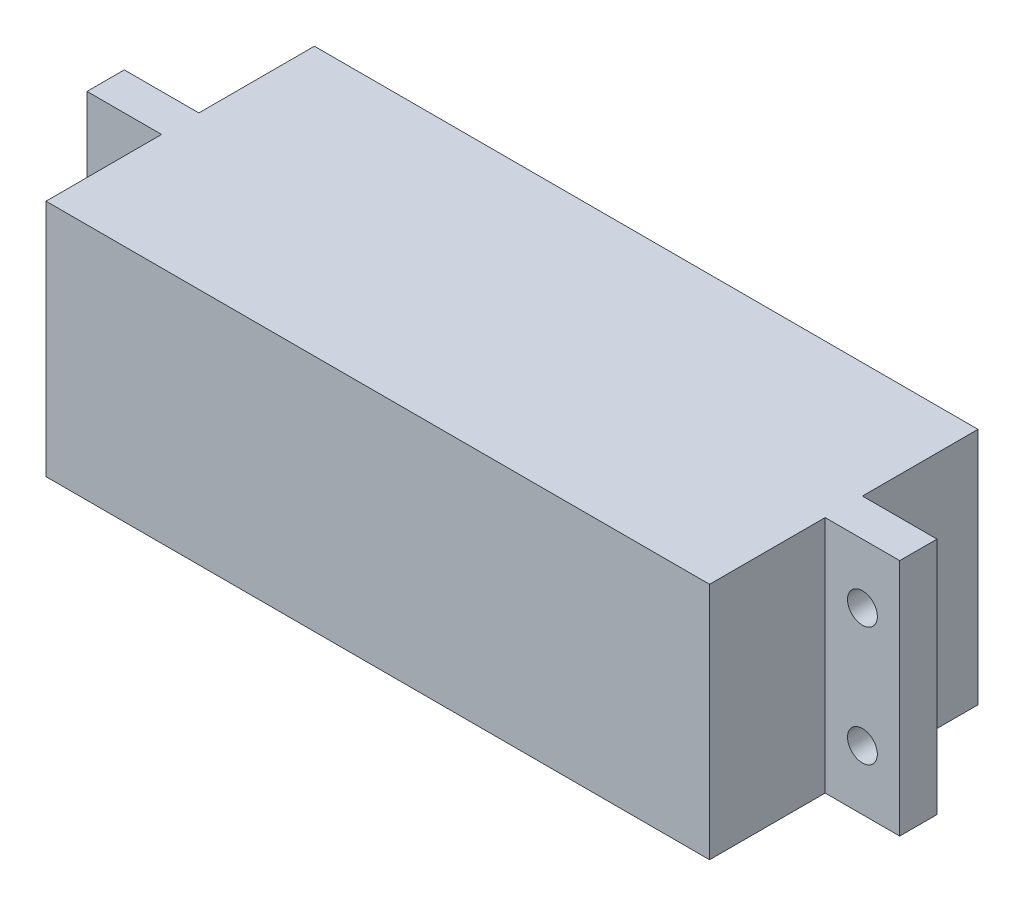
SolidWorks part; units mm, degrees
ref_plane "Front Plane" through (0, 0, 0) normal (0, 0, 1) x (1, 0, 0)
ref_plane "Top Plane" through (0, 0, 0) normal (0, 1, 0) x (1, 0, 0)
ref_plane "Right Plane" through (0, 0, 0) normal (1, 0, 0) x (0, 0, -1)
sketch "Sketch2" plane through (0, 0, 0) normal (0, 1, 0) x (1, 0, 0)
  line L1 (-42.5, -16) -> (42.5, -16)
  line L2 (-42.5, -16) -> (-42.5, 16)
  line L3 (-42.5, 16) -> (42.5, 16)
  line L4 (42.5, -16) -> (42.5, 16)
  line L5 (-42.5, -16) -> (42.5, 16) construction
  line L6 (-42.5, 16) -> (42.5, -16) construction
  point P0 (0, 0)
  dimension "D1" = 85
  dimension "D2" = 32
extrude "Boss-Extrude1" add sketch "Sketch2" along normal blind 2
extrude "Extrude-Thin1" add sketch "Sketch2<2>" along normal up to surface (2 mm away) and the other way blind 30 thin up to face at (0, 2, 0) thin type one direction wall 2
sketch "Sketch2<2>" plane through (0, 0, 0) normal (0, 1, 0) x (1, 0, 0) same geometry as "Sketch2"
sketch "Sketch3" plane through (44.5, 0, 0) normal (1, 0, 0) x (0, 0, -1)
  line L0 (18, 2) -> (-18, 2) construction
  line L1 (-2.5, 2) -> (2.5, 2)
  line L2 (-2.5, 2) -> (-2.5, -30)
  line L3 (-2.5, -30) -> (2.5, -30)
  line L4 (2.5, 2) -> (2.5, -30)
  line L5 (-18, -30) -> (18, -30) construction
  line L6 (-2.5, 2) -> (2.5, -30) construction
  line L7 (0, -30) -> (0, 2) construction
  point P12 (0, -14)
  dimension "D1" = 5
extrude "Boss-Extrude2" add sketch "Sketch3" along normal blind 10
sketch "Sketch4" plane through (0, 0, 2.5) normal (0, 0, 1) x (1, 0, 0)
  line L0 (49.5, 2) -> (49.5, -30) construction
  line L1 (54.5, 2) -> (44.5, 2) construction
  line L2 (54.5, -30) -> (44.5, -30) construction
  line L3 (44.5, -14) -> (54.5, -14) construction
  line L4 (54.5, 2) -> (54.5, -30) construction
  circle A1 centre (49.5, -6) radius 2
  circle A3 centre (49.5, -22) radius 2
  point P15 (49.5, -14)
  dimension "D1" = 4
  dimension "D2" = 8
extrude "Cut-Extrude1" cut sketch "Sketch4" against normal through all
mirror "Mirror1" about plane through (0, 0, 0) normal (1, 0, 0) of "Boss-Extrude2", "Cut-Extrude1"
